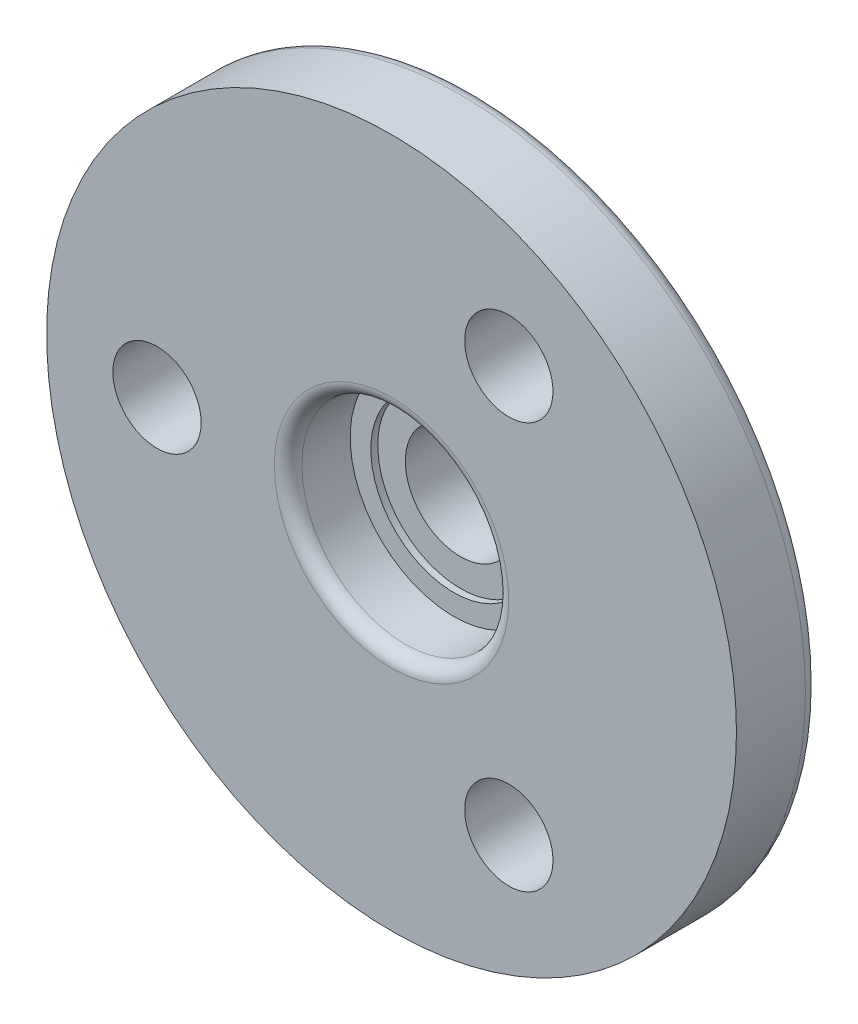
SolidWorks part; units mm, degrees
ref_plane "Ebene vorne" through (0, 0, 0) normal (0, 0, 1) x (1, 0, 0)
ref_plane "Ebene oben" through (0, 0, 0) normal (0, 1, 0) x (1, 0, 0)
ref_plane "Ebene rechts" through (0, 0, 0) normal (1, 0, 0) x (0, 0, -1)
sketch "Skizze2" plane through (0, 0, 0) normal (1, 0, 0) x (0, 0, -1)
  line L0 (0, 0) -> (99, 0) construction
  line L1 (9.5, 7) -> (8.5, 7) construction
  line L2 (9.5, 15) -> (9.5, 5) construction
  line L3 (18.5, 5) -> (9.5, 5) construction
  line L4 (18.5, 4) -> (18.5, 5) construction
  line L5 (18.5, 4) -> (7.5, 4) construction
  line L6 (7.5, 4) -> (7.5, 6) construction
  line L7 (7.5, 6) -> (7, 6) construction
  line L8 (7, 7.5) -> (7, 3) construction
  line L10 (7, 7.5) -> (2, 7.5) construction
  line L11 (2.5, 7.5) -> (2.5, 25) construction
  line L12 (8.5, 7) -> (8.5, 25) construction
  line L13 (0, 25) -> (99, 25) construction
  line L14 (0, 0) -> (99, 0) construction
  line L15 (9.5, 7) -> (8.5, 7)
  line L16 (9.5, 7) -> (9.5, 5)
  line L17 (18.5, 5) -> (9.5, 5)
  line L18 (18.5, 4) -> (18.5, 5)
  line L19 (18.5, 4) -> (7.5, 4)
  line L20 (7.5, 4) -> (7.5, 6)
  line L21 (7.5, 6) -> (7, 6)
  line L22 (7, 7.5) -> (7, 6)
  line L24 (7, 7.5) -> (2.5, 7.5)
  line L25 (2.5, 7.5) -> (2.5, 25)
  line L26 (8.5, 7) -> (8.5, 25)
  line L27 (2.5, 25) -> (8.5, 25)
revolve "Rotation1" add sketch "Skizze2" angle 360 about L14
sketch "Skizze3" plane through (0, 0, -2.5) normal (0, 0, 1) x (1, 0, 0)
  circle A0 centre (0, 0) radius 17 construction
  point P6 (-17, 0)
hole_wizard "Ø6.4 (6.4) Durchmesser Bohrung1" positions "Skizze3" profile "Skizze4" hole size "Ø6.4" standard "DIN"
sketch "Skizze4" plane through (-17, 0, -2.5) normal (1, 0, 0) x (0, -1, 0)
  line L0 (0, 0) -> (0, 11.4228)
  line L1 (0, 11.4228) -> (3.2, 9.5)
  line L2 (3.2, 9.5) -> (3.2, 0)
  line L5 (3.2, 0) -> (0, 0)
  line L10 (0, 11.4228) -> (-3.2, 9.5) construction
  line L11 (0, -6.35) -> (0, 107.95) construction
  dimension "Bohrerdurchmesser" = 6.4
  dimension "Bohrungstiefe" = 9.5
  dimension "Spitzenwinkel" = 118
pattern_circular "Kreismuster1" count 3 over 360 of "Ø6.4 (6.4) Durchmesser Bohrung1" reverse direction yes
fillet "Verrundung1" radius 1 3 edges at (5, 0, -18.5) (25, 0, -8.5) (7.5, 0, -2.5)
